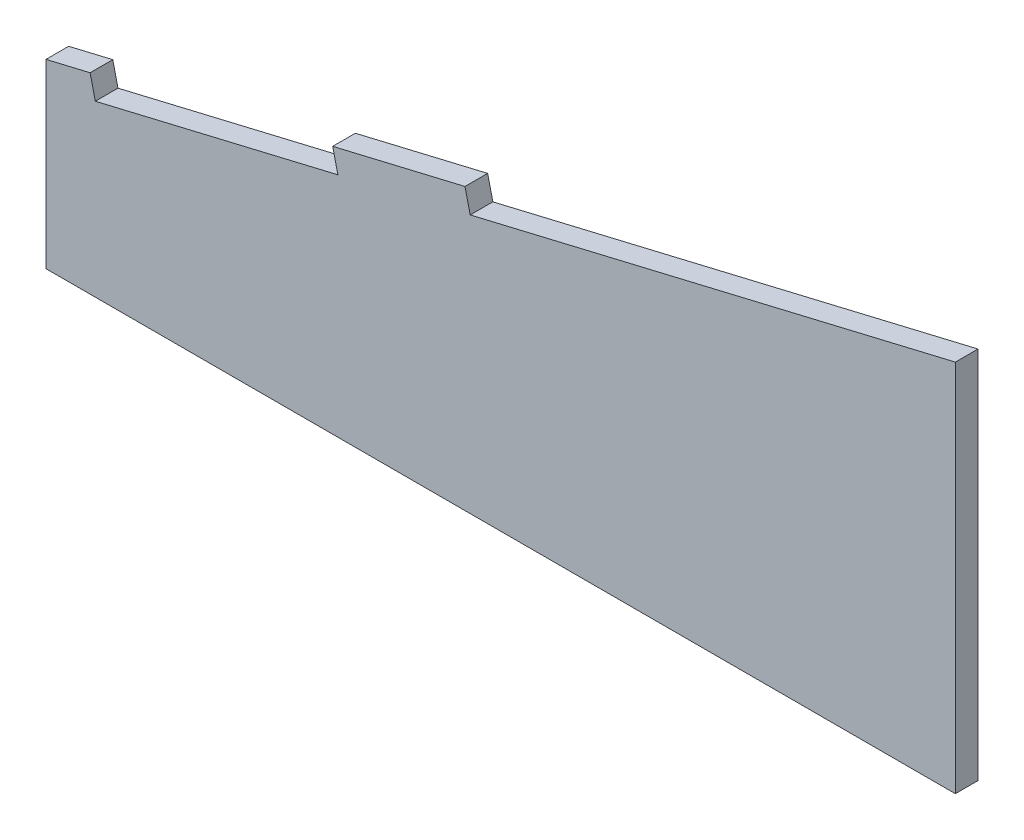
SolidWorks part; units mm, degrees
ref_plane "Front Plane" through (0, 0, 0) normal (0, 0, 1) x (1, 0, 0)
ref_plane "Top Plane" through (0, 0, 0) normal (0, 1, 0) x (1, 0, 0)
ref_plane "Right Plane" through (0, 0, 0) normal (1, 0, 0) x (0, 0, -1)
sketch "Sketch1" plane through (0, 0, 0) normal (0, 0, 1) x (1, 0, 0)
  line L0 (-1911.4418, -134.0959) -> (-1899.0849, -131.1635)
  line L4 (-1899.0849, -131.1635) -> (-1897.6187, -137.3419)
  line L5 (-1897.6187, -137.3419) -> (-1829.6562, -121.2136)
  line L6 (-1829.6562, -121.2136) -> (-1831.1224, -115.0352)
  line L7 (-1831.1224, -115.0352) -> (-1794.052, -106.238)
  line L8 (-1794.052, -106.238) -> (-1792.5858, -112.4164)
  line L9 (-1792.5858, -112.4164) -> (-1712.2665, -93.3557)
  line L13 (-1712.2665, -93.3557) -> (-1656.6608, -80.1598)
  line L16 (184.5866, 190.6964) -> (203.3772, 125.1658) construction
  line L17 (-2174.3162, -580.2088) -> (-1605.9026, -445.3177) construction
  line L18 (-1911.4418, -134.0959) -> (-1911.4418, -184.8959)
  line L19 (-1656.6608, -184.8959) -> (-1656.6608, -80.1598)
  line L20 (-1911.4418, -184.8959) -> (-1656.6608, -184.8959)
  point P12 (256.8473, 69.2881)
  point P16 (-1194.1142, -205.6961)
  point P17 (256.8473, -43.201)
  dimension "D1" = 12.7
  dimension "D2" = 6.35
  dimension "D3" = 69.85
  dimension "D4" = 38.1
  dimension "D5" = 82.55
  dimension "D6" = 57.15
  dimension "D7" = 50.8
extrude "Boss-Extrude1" add sketch "Sketch1" along normal blind 6.35 contours L18 L20 L19 L13 L9 L8 L7 L6 L5 L4 L0 region at (-1767.9963, -145.1566, 0)
